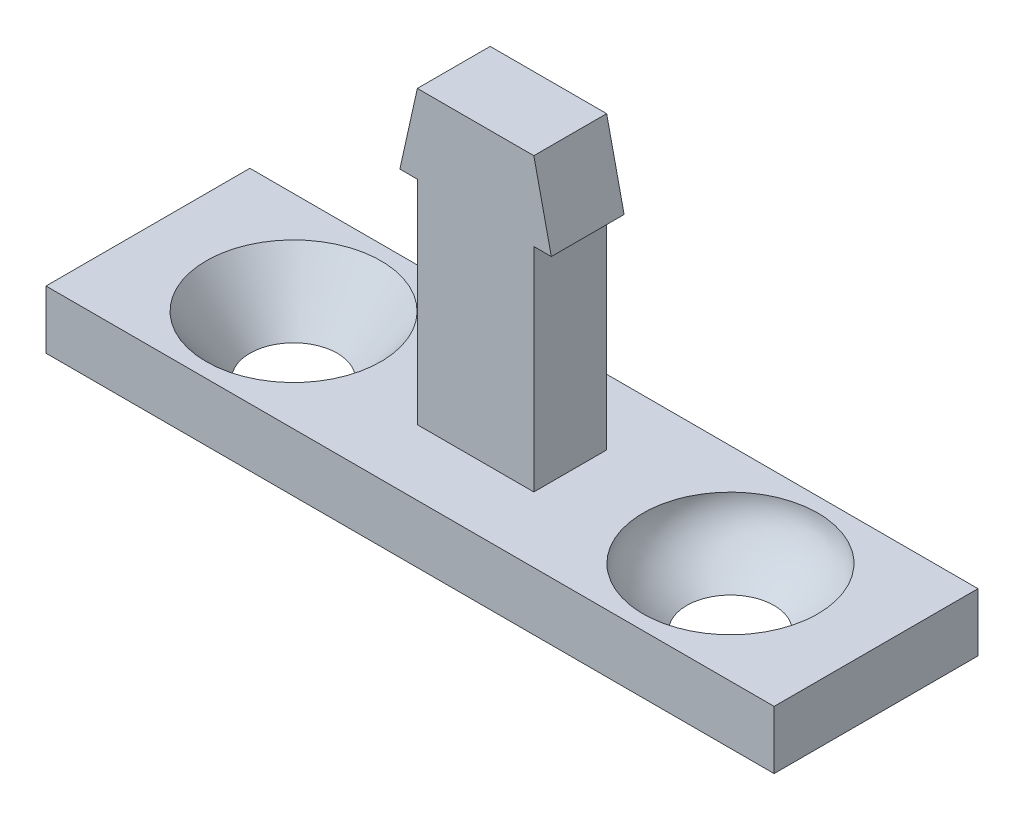
SolidWorks part; units mm, degrees
ref_plane "前视基准面" through (0, 0, 0) normal (0, 0, 1) x (1, 0, 0)
ref_plane "上视基准面" through (0, 0, 0) normal (0, 1, 0) x (1, 0, 0)
ref_plane "右视基准面" through (0, 0, 0) normal (1, 0, 0) x (0, 0, -1)
other "Configuration Table"
sketch "草图1" plane through (0, 0, 0) normal (0, 1, 0) x (1, 0, 0)
  line L1 (-12.5, -3.5) -> (12.5, -3.5)
  line L2 (-12.5, -3.5) -> (-12.5, 3.5)
  line L3 (-12.5, 3.5) -> (12.5, 3.5)
  line L4 (12.5, -3.5) -> (12.5, 3.5)
  line L5 (0, 3.5) -> (0, -3.5) construction
  line L6 (-12.5, 0) -> (12.5, 0) construction
  point P0 (0, 0)
  dimension "D1" = 7
  dimension "D2" = 25
extrude "凸台-拉伸1" add sketch "草图1" along normal blind 2
sketch "草图2" plane through (0, 2, 0) normal (0, 1, 0) x (1, 0, 0)
  circle A0 centre (-7.5, 0) radius 3
  circle A1 centre (7.5, 0) radius 3
  dimension "D3" = 6
  dimension "D1" = 15
  dimension "D2" = 7.5
sketch "草图3" plane through (0, 0, 0) normal (0, -1, 0) x (1, 0, 0)
  circle A0 centre (-7.5, 0) radius 1.5
  circle A1 centre (7.5, 0) radius 1.5
  dimension "D1" = 3
loft "切除-放样1" cut section "草图2" section "草图3" start constraint normal to profile start tangent length 1 connector at (10.288, 2, 1.1077) connector at (8.8612, 0, 0.6301)
loft "切除-放样2" cut section "草图2<6>" section "草图3<4>" connector at (-4.8117, 2, -1.3317) connector at (-6.2782, 0, -0.8702)
sketch "草图2<6>" plane through (0, 2, 0) normal (0, 1, 0) x (1, 0, 0) same geometry as "草图2"
sketch "草图3<4>" plane through (0, 0, 0) normal (0, -1, 0) x (1, 0, 0) same geometry as "草图3"
sketch "草图4" plane through (0, 2, 0) normal (0, 1, 0) x (1, 0, 0)
  line L1 (-2, -1.25) -> (2, -1.25)
  line L2 (-2, -1.25) -> (-2, 1.25)
  line L3 (-2, 1.25) -> (2, 1.25)
  line L4 (2, -1.25) -> (2, 1.25)
  line L5 (0, 1.25) -> (0, -1.25) construction
  line L6 (-2, 0) -> (2, 0) construction
  point P0 (0, 0)
  dimension "D1" = 2.5
  dimension "D2" = 4
extrude "凸台-拉伸2" add sketch "草图4" along normal blind 10
sketch "草图5" plane through (0, 0, -1.25) normal (0, 0, -1) x (-1, 0, 0)
  line L0 (-2, 12) -> (-2.6, 9.3)
  line L1 (-2.6, 9.3) -> (-2, 9.3)
  line L2 (2.6, 9.3) -> (2, 12)
  line L4 (-2, 12) -> (-2, 9.3)
  line L5 (2, 12) -> (2, 9.3)
  line L6 (2, 9.3) -> (2.6, 9.3)
  line L7 (-2, 12) -> (2, 12) construction
  point P6 (-2, 10.6866)
  point P9 (2.4522, 10.6487)
  dimension "D1" = 5.2
  dimension "D2" = 2.7
extrude "凸台-拉伸3" add sketch "草图5" against normal up to surface (2.5 mm away) up to face at (0, 7, 1.25)
